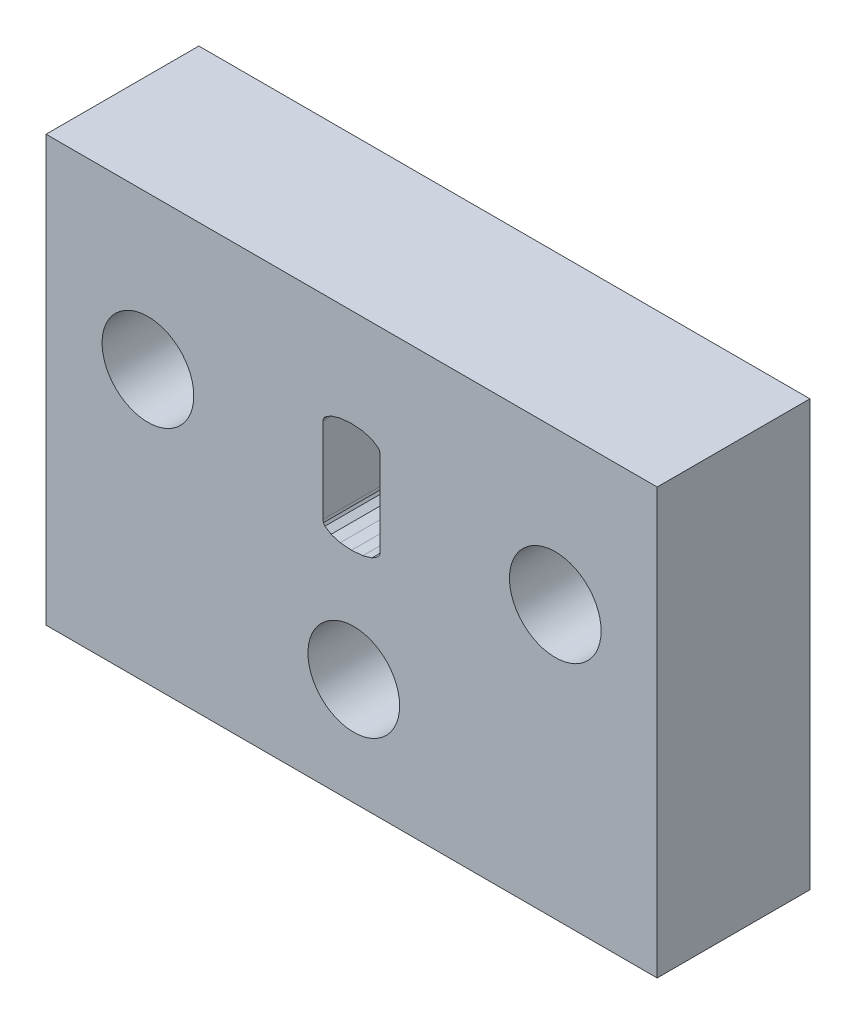
SolidWorks part; units mm, degrees
ref_plane "Plano frontal" through (0, 0, 0) normal (0, 0, 1) x (1, 0, 0)
ref_plane "Plano superior" through (0, 0, 0) normal (0, 1, 0) x (1, 0, 0)
ref_plane "Plano direito" through (0, 0, 0) normal (1, 0, 0) x (0, 0, -1)
sketch "Model" plane through (0, 0, 0) normal (0, 0, 1) x (1, 0, 0)
  line L0 (31.7767, 24.0536) -> (55.7767, 24.0536)
  line L1 (31.7767, 7.3536) -> (31.7767, 24.0536)
  line L2 (55.7767, 24.0536) -> (55.7767, 7.3536)
  line L3 (55.7767, 7.3536) -> (31.7767, 7.3536)
  line L4 (42.6491, 16.3825) -> (42.6692, 16.2863)
  line L5 (42.6692, 16.2863) -> (42.7295, 16.1975)
  line L6 (42.7295, 16.1975) -> (42.9707, 16.0422)
  line L7 (42.9707, 16.0422) -> (43.3321, 15.9369)
  line L8 (43.3321, 15.9369) -> (43.773, 15.9018)
  line L9 (43.773, 15.9018) -> (44.214, 15.9369)
  line L10 (44.214, 15.9369) -> (44.5754, 16.0422)
  line L11 (44.5754, 16.0422) -> (44.8166, 16.1975)
  line L12 (44.8166, 16.1975) -> (44.8769, 16.2863)
  line L13 (44.8769, 16.2863) -> (44.897, 16.3825)
  line L14 (44.897, 16.3825) -> (44.897, 19.7289)
  line L15 (44.897, 19.7289) -> (44.8769, 19.8251)
  line L16 (44.8769, 19.8251) -> (44.8166, 19.9139)
  line L17 (44.8166, 19.9139) -> (44.5754, 20.0692)
  line L18 (44.5754, 20.0692) -> (44.214, 20.1746)
  line L19 (44.214, 20.1746) -> (43.773, 20.2097)
  line L20 (43.773, 20.2097) -> (43.3321, 20.1746)
  line L21 (43.3321, 20.1746) -> (42.9707, 20.0692)
  line L22 (42.9707, 20.0692) -> (42.7295, 19.9139)
  line L23 (42.7295, 19.9139) -> (42.6692, 19.8251)
  line L24 (42.6692, 19.8251) -> (42.6491, 19.7289)
  line L25 (42.6491, 19.7289) -> (42.6491, 16.3825)
  line L26 (44.897, 16.3825) -> (44.8769, 16.2863)
  line L27 (44.8769, 16.2863) -> (44.8166, 16.1975)
  line L28 (44.8166, 16.1975) -> (44.5754, 16.0422)
  line L29 (44.5754, 16.0422) -> (44.214, 15.9369)
  line L30 (44.214, 15.9369) -> (43.773, 15.9018)
  line L31 (43.773, 15.9018) -> (43.3321, 15.9369)
  line L32 (43.3321, 15.9369) -> (42.9707, 16.0422)
  line L33 (42.9707, 16.0422) -> (42.7295, 16.1975)
  line L34 (42.7295, 16.1975) -> (42.6692, 16.2863)
  line L35 (42.6692, 16.2863) -> (42.6491, 16.3825)
  line L36 (42.6491, 16.3825) -> (42.6491, 19.7289)
  line L37 (42.6491, 19.7289) -> (42.6692, 19.8251)
  line L38 (42.6692, 19.8251) -> (42.7295, 19.9139)
  line L39 (42.7295, 19.9139) -> (42.9707, 20.0692)
  line L40 (42.9707, 20.0692) -> (43.3321, 20.1746)
  line L41 (43.3321, 20.1746) -> (43.773, 20.2097)
  line L42 (43.773, 20.2097) -> (44.214, 20.1746)
  line L43 (44.214, 20.1746) -> (44.5754, 20.0692)
  line L44 (44.5754, 20.0692) -> (44.8166, 19.9139)
  line L45 (44.8166, 19.9139) -> (44.8769, 19.8251)
  line L46 (44.8769, 19.8251) -> (44.897, 19.7289)
  line L47 (44.897, 19.7289) -> (44.897, 16.3825)
  circle A0 centre (51.7756, 18.0536) radius 1.8
  circle A1 centre (43.8614, 11.5536) radius 1.8
  circle A2 centre (35.7767, 18.0536) radius 1.8
extrude "Ressalto-extrusão1" add sketch "Model" along normal blind 6 contours L3 L2 L0 L1 A2 A1 A0 L25 L24 L23 L22 L21 L20 L19 L18 L17 L16 L15 L14 L13 L12 L11 L10 L9 L8 L7 L6 L5 L4 region at (43.7744, 15.6281, 0)
